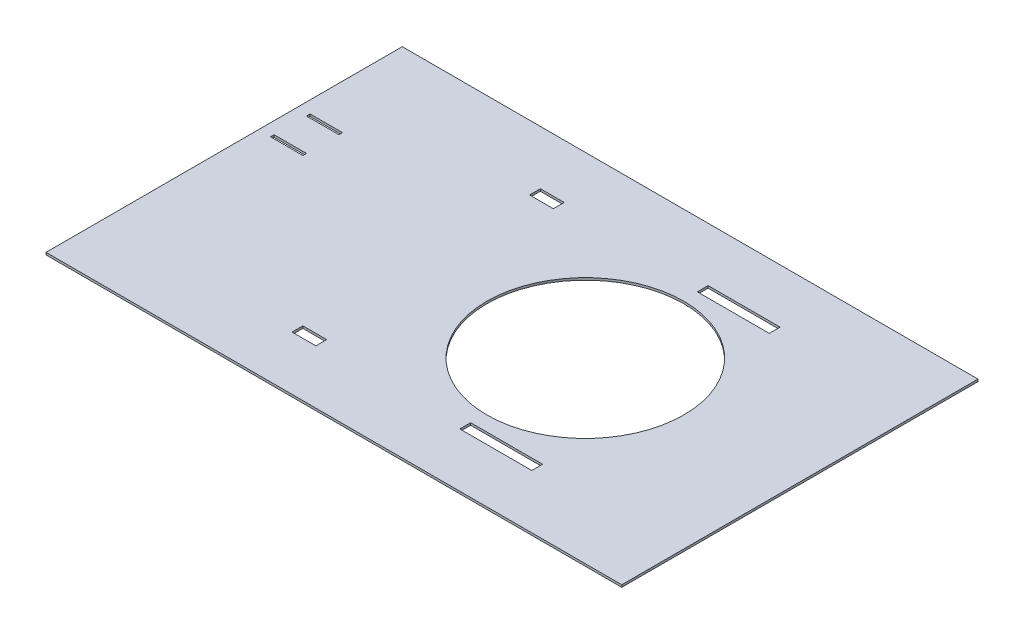
SolidWorks part; units mm, degrees
ref_plane "Front Plane" through (0, 0, 0) normal (0, 0, 1) x (1, 0, 0)
ref_plane "Top Plane" through (0, 0, 0) normal (0, 1, 0) x (1, 0, 0)
ref_plane "Right Plane" through (0, 0, 0) normal (1, 0, 0) x (0, 0, -1)
sketch "Sketch1" plane through (0, 0, 0) normal (0, 1, 0) x (1, 0, 0)
  line L1 (-368.707, 248.2819) -> (-368.707, -230.8741)
  line L2 (-368.707, -230.8741) -> (405.692, -230.8741)
  line L3 (405.692, -230.8741) -> (405.692, 248.2819)
  line L4 (405.692, 248.2819) -> (-368.707, 248.2819)
  line L5 (115.2878, 175.6705) -> (212.0864, 175.6705)
  line L6 (212.0864, 175.6705) -> (212.0864, 161.149)
  line L7 (212.0864, 161.149) -> (115.2878, 161.149)
  line L8 (115.2878, 161.149) -> (115.2878, 175.6705)
  line L9 (-308.785, 54.683) -> (-352.3496, 54.683)
  line L10 (-352.3496, 54.683) -> (-352.3496, 59.5268)
  line L11 (-352.3496, 59.5268) -> (-308.785, 59.5268)
  line L12 (-308.785, 59.5268) -> (-308.785, 54.683)
  line L13 (-308.785, 103.0915) -> (-352.3496, 103.0915)
  line L14 (-352.3496, 103.0915) -> (-352.3496, 107.932)
  line L15 (-352.3496, 107.932) -> (-308.785, 107.932)
  line L16 (-308.785, 107.932) -> (-308.785, 103.0915)
  line L17 (-78.3111, -158.2713) -> (-110.3539, -158.2713)
  line L18 (-110.3539, -158.2713) -> (-110.3539, -143.7498)
  line L19 (-110.3539, -143.7498) -> (-78.3111, -143.7498)
  line L20 (-78.3111, -143.7498) -> (-78.3111, -158.2713)
  line L21 (-78.3111, 161.161) -> (-110.3539, 161.161)
  line L22 (-110.3539, 161.161) -> (-110.3539, 175.6825)
  line L23 (-110.3539, 175.6825) -> (-78.3111, 175.6825)
  line L24 (-78.3111, 175.6825) -> (-78.3111, 161.161)
  line L25 (212.0931, -158.2713) -> (115.2928, -158.2713)
  line L26 (115.2928, -158.2713) -> (115.2928, -143.7498)
  line L27 (115.2928, -143.7498) -> (212.0931, -143.7498)
  line L28 (212.0931, -143.7498) -> (212.0931, -158.2713)
  circle A0 centre (117.1318, 8.695) radius 132.5
extrude "Boss-Extrude1" add sketch "Sketch1" along normal blind 3
